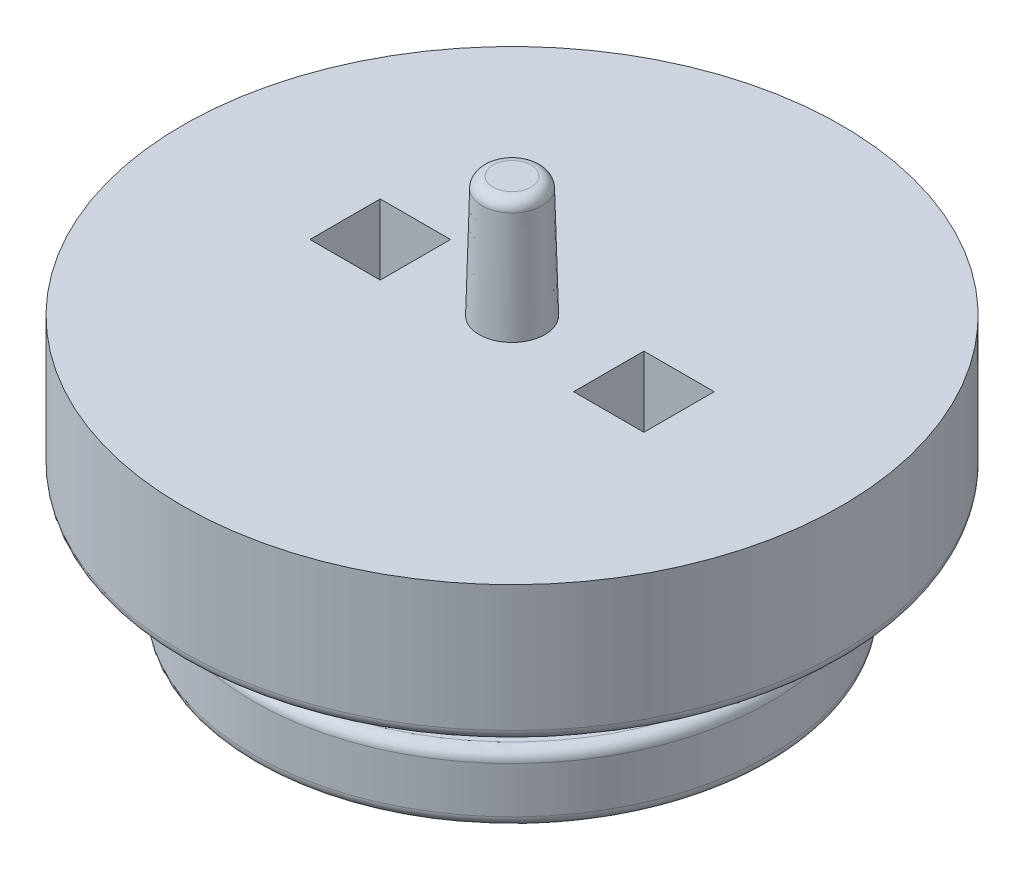
SolidWorks part; units mm, degrees
ref_plane "Front Plane" through (0, 0, 0) normal (0, 0, 1) x (1, 0, 0)
ref_plane "Top Plane" through (0, 0, 0) normal (0, 1, 0) x (1, 0, 0)
ref_plane "Right Plane" through (0, 0, 0) normal (1, 0, 0) x (0, 0, -1)
sketch "Sketch1" plane through (0, 0, 0) normal (0, 1, 0) x (1, 0, 0)
  circle A0 centre (0, 0) radius 5.75
  dimension "D1" = 11.5
extrude "Boss-Extrude1" add sketch "Sketch1" along normal blind 15
ref_plane "Plane1" through (0, 0, -5.75) normal (0, 0, -1) x (-1, 0, 0)
sketch "Sketch12" plane through (0, 15, 0) normal (0, 1, 0) x (1, 0, 0)
  circle A0 centre (0, 0) radius 5.75
  circle A1 centre (0, 0) radius 5.75 construction
extrude "Boss-Extrude3" add sketch "Sketch12" along normal blind 2
sketch "Sketch11" plane through (0, 17, 0) normal (0, 1, 0) x (1, 0, 0)
  line L0 (6, 0) -> (0, 0) construction
  line L1 (-7.6, 1.6) -> (-4.4, 1.6)
  line L2 (-7.6, 1.6) -> (-7.6, -1.6)
  line L3 (-7.6, -1.6) -> (-4.4, -1.6)
  line L4 (-4.4, 1.6) -> (-4.4, -1.6)
  line L5 (-7.6, 1.6) -> (-4.4, -1.6) construction
  line L6 (-7.6, -1.6) -> (-4.4, 1.6) construction
  line L7 (4.4, 1.6) -> (7.6, 1.6)
  line L8 (4.4, 1.6) -> (4.4, -1.6)
  line L9 (4.4, -1.6) -> (7.6, -1.6)
  line L10 (7.6, 1.6) -> (7.6, -1.6)
  line L11 (4.4, 1.6) -> (7.6, -1.6) construction
  line L12 (4.4, -1.6) -> (7.6, 1.6) construction
  line L13 (0, 0) -> (-6, 0) construction
  circle A0 centre (0, 0) radius 15
  point P0 (-6, 0)
  point P5 (6, 0)
  circle M22 centre (0, 0) radius 5.75
  dimension "D4" = 30
  dimension "D1" = 3.2
  dimension "D2" = 3.2
  dimension "D3" = 6
  dimension "D5" = 3.2
  dimension "D6" = 3.2
extrude "Boss-Extrude2" add sketch "Sketch11" along normal blind 4.25
sketch "Sketch13" plane through (0, 21.25, 0) normal (0, 1, 0) x (1, 0, 0)
  circle A0 centre (0, 0) radius 1.5
  dimension "D1" = 3
extrude "Boss-Extrude4" add sketch "Sketch13" along normal blind 5.5 draft 1.5
fillet "Fillet2" radius 0.5 1 edges at (0, 26.75, 1.356)
extrude "Boss-Extrude5" add sketch "Sketch11<2>" against normal blind 2 contours A0 L7 L10 L9 L3 L2 L1 M22 | L10 L7 L9 M22 | L2 L3 L1 M22 region at (-6.6363, 17, 0) region at (6.6363, 17, 0) region at (-14.5757, 17, 0)
sketch "Sketch11<2>" plane through (0, 17, 0) normal (0, 1, 0) x (1, 0, 0) same geometry as "Sketch11"
sketch "Sketch14" plane through (0, 0, 0) normal (0, -1, 0) x (1, 0, 0)
  circle A1 centre (0, 0) radius 11.75
  dimension "D1" = 23.5
extrude "Boss-Extrude6" add sketch "Sketch14" against normal offset from surface (12.4 mm away) 2.6 up to face at (0, 15, 5.75)
extrude "Cut-Extrude1" cut sketch "Sketch14<2>" against normal offset from surface (9.3 mm away) 3.1 up to face at (0, 12.4, 5.75)
sketch "Sketch14<2>" plane through (0, 0, 0) normal (0, -1, 0) x (1, 0, 0) same geometry as "Sketch14"
fillet "Fillet3" radius 0.5 3 edges at (0, 9.3, 11.75) (0, 12.4, 11.75) (0, 15, 15)
